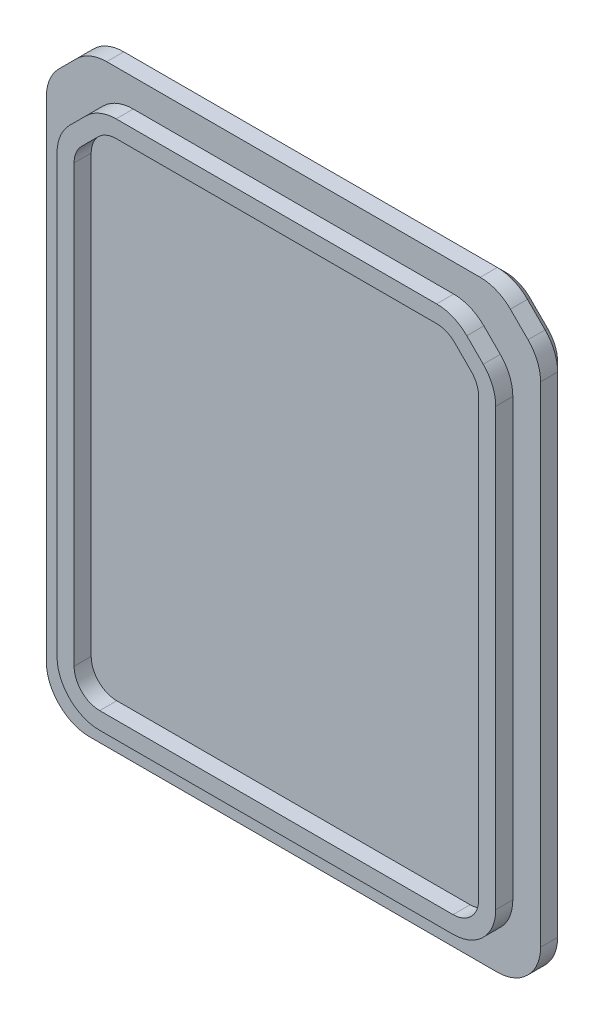
SolidWorks part; units mm, degrees
ref_plane "Front Plane" through (0, 0, 0) normal (0, 0, 1) x (1, 0, 0)
ref_plane "Top Plane" through (0, 0, 0) normal (0, 1, 0) x (1, 0, 0)
ref_plane "Right Plane" through (0, 0, 0) normal (1, 0, 0) x (0, 0, -1)
sketch "Sketch2" plane through (0, 0, -21.645) normal (0, 0, -1) x (-1, 0, 0)
  line L16 (21.4289, 45.48) -> (-22.3079, 45.48)
  line L18 (-29.379, 38.4089) -> (-29.379, -18.9289)
  line L20 (-24.3079, -24) -> (23.4289, -24)
  line L22 (28.5, -18.9289) -> (28.5, 38.4089)
  line L24 (21.4289, 45.48) -> (-22.3079, 45.48)
  line L26 (-29.379, 38.4089) -> (-29.379, -18.9289)
  line L28 (-24.3079, -24) -> (23.4289, -24)
  line L30 (28.5, -18.9289) -> (28.5, 38.4089)
  line L60 (-25.8435, 44.0155) -> (-27.9145, 41.9445)
  line L61 (-25.8435, 44.0155) -> (-27.9145, 41.9445)
  line L62 (-27.9145, -22.4645) -> (-27.8435, -22.5355)
  line L63 (-27.9145, -22.4645) -> (-27.8435, -22.5355)
  line L64 (26.9645, -22.5355) -> (27.0355, -22.4645)
  line L65 (26.9645, -22.5355) -> (27.0355, -22.4645)
  line L66 (27.0355, 41.9445) -> (24.9645, 44.0155)
  line L67 (27.0355, 41.9445) -> (24.9645, 44.0155)
  arc A52 (-22.3079, 45.48) -> (-25.8435, 44.0155) centre (-22.3079, 40.48) ccw
  arc A53 (-22.3079, 45.48) -> (-25.8435, 44.0155) centre (-22.3079, 40.48) ccw
  arc A54 (-27.9145, 41.9445) -> (-29.379, 38.4089) centre (-24.379, 38.4089) ccw
  arc A55 (-27.9145, 41.9445) -> (-29.379, 38.4089) centre (-24.379, 38.4089) ccw
  arc A56 (-29.379, -18.9289) -> (-27.9145, -22.4645) centre (-24.379, -18.9289) ccw
  arc A57 (-29.379, -18.9289) -> (-27.9145, -22.4645) centre (-24.379, -18.9289) ccw
  arc A58 (-27.8435, -22.5355) -> (-24.3079, -24) centre (-24.3079, -19) ccw
  arc A59 (-27.8435, -22.5355) -> (-24.3079, -24) centre (-24.3079, -19) ccw
  arc A60 (23.4289, -24) -> (26.9645, -22.5355) centre (23.4289, -19) ccw
  arc A61 (23.4289, -24) -> (26.9645, -22.5355) centre (23.4289, -19) ccw
  arc A62 (27.0355, -22.4645) -> (28.5, -18.9289) centre (23.5, -18.9289) ccw
  arc A63 (27.0355, -22.4645) -> (28.5, -18.9289) centre (23.5, -18.9289) ccw
  arc A64 (28.5, 38.4089) -> (27.0355, 41.9445) centre (23.5, 38.4089) ccw
  arc A65 (28.5, 38.4089) -> (27.0355, 41.9445) centre (23.5, 38.4089) ccw
  arc A66 (24.9645, 44.0155) -> (21.4289, 45.48) centre (21.4289, 40.48) ccw
  arc A67 (24.9645, 44.0155) -> (21.4289, 45.48) centre (21.4289, 40.48) ccw
  dimension "D1" = 0
extrude "Boss-Extrude1" add sketch "Sketch2" along normal blind 3
sketch "Sketch3" plane through (0, 0, -21.645) normal (0, 0, -1) x (-1, 0, 0)
  line L16 (-24.129, -18.75) -> (23.25, -18.75)
  line L17 (23.25, -18.75) -> (23.25, 36.548)
  line L18 (23.25, 36.548) -> (19.568, 40.23)
  line L19 (19.568, 40.23) -> (-20.447, 40.23)
  line L20 (-20.447, 40.23) -> (-24.129, 36.548)
  line L21 (-24.129, 36.548) -> (-24.129, -18.75)
  line L100 (-26.129, -20.75) -> (25.25, -20.75)
  line L101 (25.25, -20.75) -> (25.25, 37.3764)
  line L102 (-26.129, 37.3764) -> (-26.129, -20.75)
  line L103 (20.3964, 42.23) -> (-21.2754, 42.23)
  line L104 (25.25, 37.3764) -> (20.3964, 42.23)
  line L105 (-21.2754, 42.23) -> (-26.129, 37.3764)
  line L106 (-26.129, -20.75) -> (25.25, -20.75)
  line L107 (25.25, -20.75) -> (25.25, 37.3764)
  line L108 (-26.129, 37.3764) -> (-26.129, -20.75)
  line L109 (20.3964, 42.23) -> (-21.2754, 42.23)
  line L110 (25.25, 37.3764) -> (20.3964, 42.23)
  line L111 (-21.2754, 42.23) -> (-26.129, 37.3764)
  dimension "D1" = 2
  dimension "D2" = 0.25
extrude "Boss-Extrude2" add sketch "Sketch3" against normal blind 2
chamfer "Chamfer1" distance 1 angle 45 16 edges at (-26, 42.98, -24.645) (-28.1194, 40.3223, -24.645) (-28.5, 9.74, -24.645) (-28.1194, -20.8423, -24.645) (-27, -22.5, -24.645) (-25.3423, -23.6194, -24.645) (0.4395, -24, -24.645) (26.2213, -23.6194, -24.645) (27.879, -22.5, -24.645) (28.9984, -20.8423, -24.645) (29.379, 9.74, -24.645) (28.9984, 40.3223, -24.645) (26.879, 42.98, -24.645) (24.2213, 45.0994, -24.645) (0.4395, 45.48, -24.645) (-23.3423, 45.0994, -24.645)
fillet "Fillet1" radius 3 6 edges at (-19.568, 40.23, -20.645) (-23.25, 36.548, -20.645) (24.129, 36.548, -20.645) (20.447, 40.23, -20.645) (24.129, -18.75, -20.645) (-23.25, -18.75, -20.645)
fillet "Fillet2" radius 5 6 edges at (-25.25, 37.3764, -20.645) (-20.3964, 42.23, -20.645) (21.2754, 42.23, -20.645) (26.129, 37.3764, -20.645) (-25.25, -20.75, -20.645) (26.129, -20.75, -20.645)
